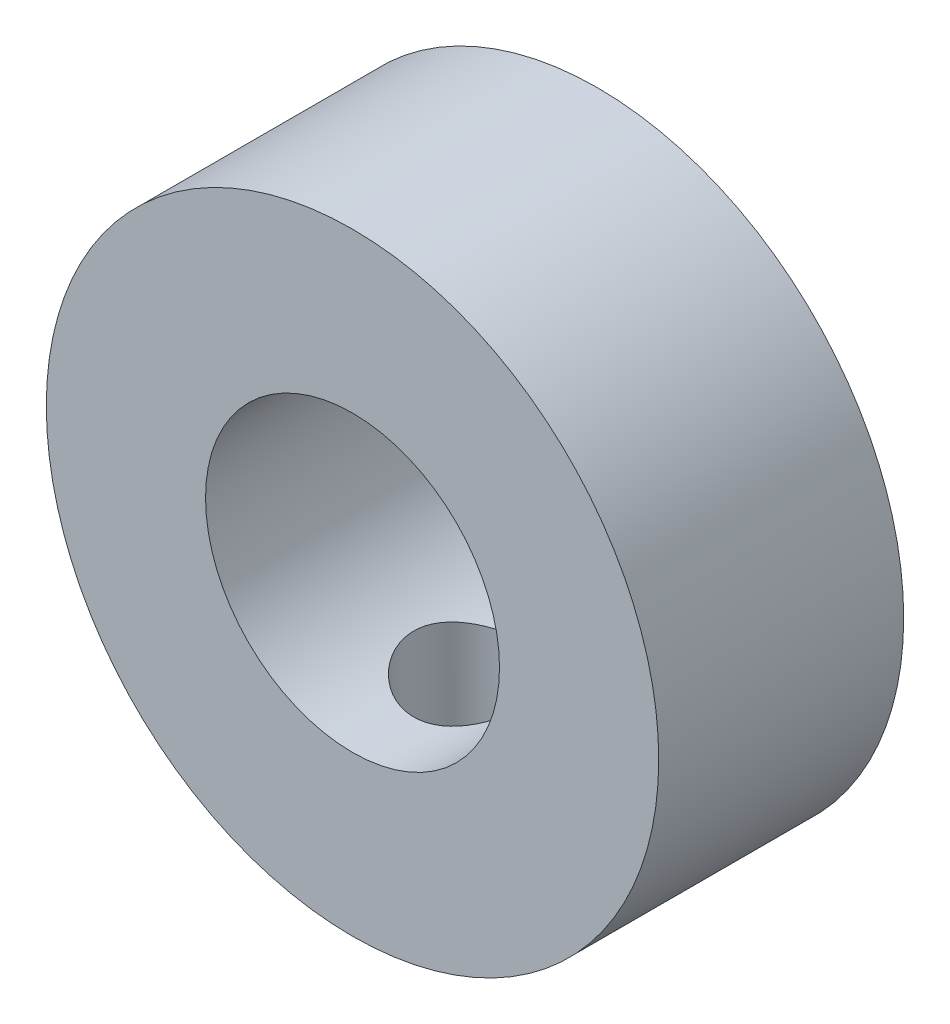
SolidWorks part; units mm, degrees
ref_plane "前视基准面" through (0, 0, 0) normal (0, 0, 1) x (1, 0, 0)
ref_plane "上视基准面" through (0, 0, 0) normal (0, 1, 0) x (1, 0, 0)
ref_plane "右视基准面" through (0, 0, 0) normal (1, 0, 0) x (0, 0, -1)
sketch "草图1" plane through (0, 0, 0) normal (0, 0, 1) x (1, 0, 0)
  circle A0 centre (0, 0) radius 6
  circle A1 centre (0, 0) radius 12.5
  dimension "D1" = 12
  dimension "D2" = 25
extrude "凸台-拉伸1" add sketch "草图1" along normal blind 10
sketch "草图2" plane through (0, 0, 0) normal (0, 1, 0) x (1, 0, 0)
  line L0 (0, 0) -> (0, -10) construction
  line L1 (-12.5, -10) -> (12.5, -10) construction
  circle A0 centre (0, -5) radius 2.5
  dimension "D1" = 5
extrude "切除-拉伸1" cut sketch "草图2" against normal through all and the other way blind 10
